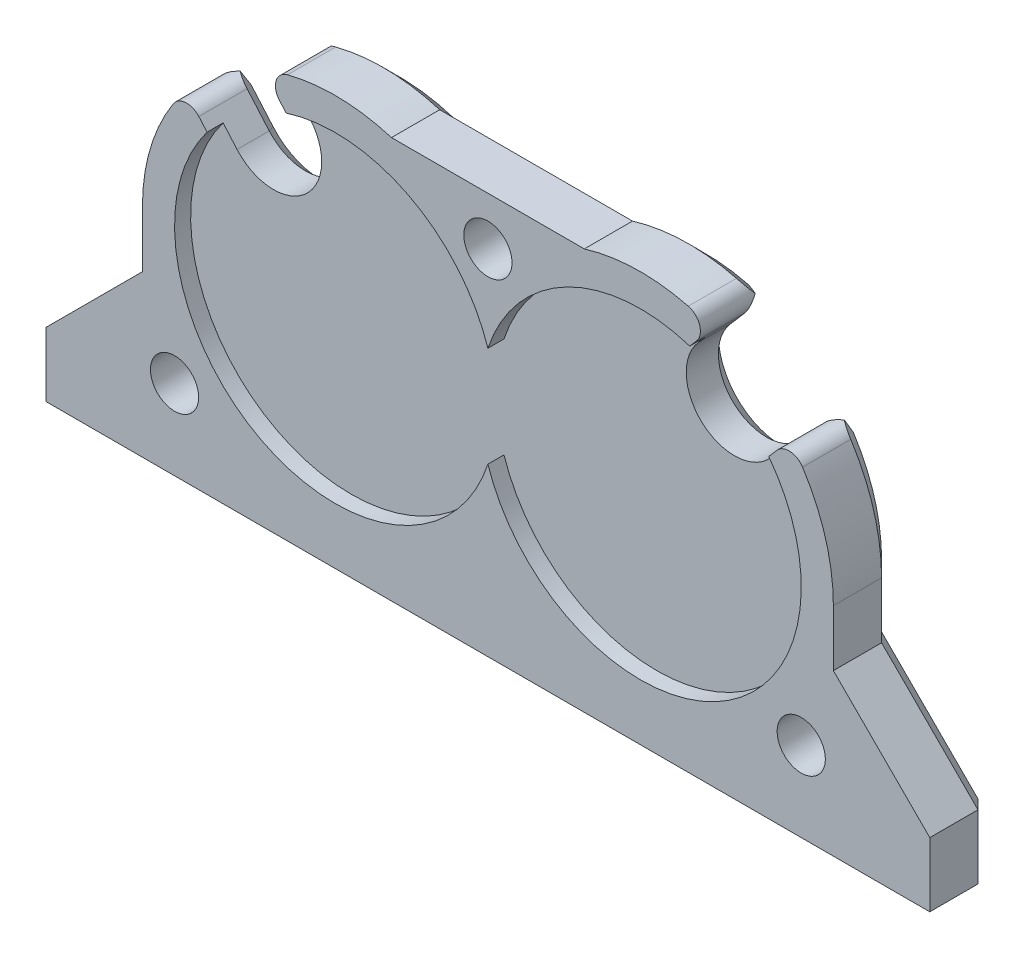
SolidWorks part; units mm, degrees
material "ABS"
ref_plane "Front Plane" through (0, 0, 0) normal (0, 0, 1) x (1, 0, 0)
ref_plane "Top Plane" through (0, 0, 0) normal (0, 1, 0) x (1, 0, 0)
ref_plane "Right Plane" through (0, 0, 0) normal (1, 0, 0) x (0, 0, -1)
sketch "Sketch1" plane through (0, 0, 0) normal (0, 0, 1) x (1, 0, 0)
  line L0 (-27.5, 0) -> (27.5, 0) construction
  line L1 (-27.5, 0) -> (-21.5, 6)
  line L2 (27.5, 0) -> (21.5, 6)
  line L3 (-9.5, 9.5) -> (9.5, 9.5) construction
  line L4 (-6, 20.9782) -> (6, 20.9782)
  line L5 (21.5, 9.5) -> (21.5, 6)
  line L6 (-21.5, 6) -> (-21.5, 9.5)
  line L7 (-27.5, 0) -> (-27.5, -4)
  line L8 (-27.5, -4) -> (27.5, -4)
  line L9 (27.5, -4) -> (27.5, 0)
  circle A0 centre (-9.5, 9.5) radius 10
  circle A1 centre (9.5, 9.5) radius 10
  arc A2 (1.1579, 3.9855) -> (1.1579, 15.0145) centre (-9.5, 9.5) ccw
  arc A3 (21.5, 9.5) -> (6, 20.9782) centre (9.5, 9.5) ccw
  arc A4 (-16.8314, 0) -> (-2.1686, 0) centre (-9.5, 9.5) ccw construction
  arc A5 (-21.5, 9.5) -> (-16.8314, 0) centre (-9.5, 9.5) ccw construction
  arc A6 (-2.1686, 0) -> (0, 2.1686) centre (-9.5, 9.5) ccw construction
  arc A7 (0, 2.1686) -> (2.1686, 0) centre (9.5, 9.5) ccw construction
  arc A8 (2.1686, 0) -> (16.8314, 0) centre (9.5, 9.5) ccw construction
  arc A9 (16.8314, 0) -> (21.5, 9.5) centre (9.5, 9.5) ccw construction
  arc A10 (0, 2.1686) -> (1.1579, 3.9855) centre (-9.5, 9.5) ccw construction
  arc A11 (-1.1579, 3.9855) -> (0, 2.1686) centre (9.5, 9.5) ccw construction
  arc A12 (6, 20.9782) -> (0, 16.8314) centre (9.5, 9.5) ccw construction
  arc A13 (-1.1579, 15.0145) -> (-1.1579, 3.9855) centre (9.5, 9.5) ccw
  arc A14 (0, 16.8314) -> (-6, 20.9782) centre (-9.5, 9.5) ccw construction
  arc A15 (-6, 20.9782) -> (-21.5, 9.5) centre (-9.5, 9.5) ccw
  arc A16 (0, 16.8314) -> (-1.1579, 15.0145) centre (9.5, 9.5) ccw construction
  arc A17 (1.1579, 15.0145) -> (0, 16.8314) centre (-9.5, 9.5) ccw construction
  point P2 (0, 0)
  point P10 (0, 9.5)
  point P22 (0, 20.9782)
  dimension "D1" = 20
  dimension "D5" = 2
  dimension "D2" = 19
  dimension "D3" = 6
  dimension "D4" = 12
  dimension "D6" = 9.5
  dimension "D7" = 4
extrude "Boss-Extrude1" add sketch "Sketch1" along normal blind 1 contours L4 A15 L6 L1 L0 L2 L5 A3 A0 A1
sketch "Sketch2" plane through (0, 0, 0) normal (0, 0, -1) x (-1, 0, 0)
  line L6 (6, 20.9782) -> (-6, 20.9782)
  line L7 (-21.5, 9.5) -> (-21.5, 6)
  line L8 (-21.5, 6) -> (-27.5, 0)
  line L9 (-27.5, 0) -> (-27.5, -4)
  line L10 (27.5, 0) -> (21.5, 6)
  line L11 (21.5, 6) -> (21.5, 9.5)
  line L12 (6, 20.9782) -> (-6, 20.9782)
  line L13 (-21.5, 9.5) -> (-21.5, 6)
  line L14 (-21.5, 6) -> (-27.5, 0)
  line L16 (27.5, 0) -> (21.5, 6)
  line L17 (21.5, 6) -> (21.5, 9.5)
  line L20 (-27.5, 0) -> (-27.5, -4)
  line L21 (-27.5, -4) -> (27.5, -4)
  line L22 (-27.5, -4) -> (27.5, -4)
  line L23 (27.5, -4) -> (27.5, 0)
  line L24 (27.5, -4) -> (27.5, 0)
  arc A2 (-6, 20.9782) -> (-21.5, 9.5) centre (-9.5, 9.5) ccw
  arc A3 (21.5, 9.5) -> (6, 20.9782) centre (9.5, 9.5) ccw
  arc A4 (-6, 20.9782) -> (-21.5, 9.5) centre (-9.5, 9.5) ccw
  arc A5 (21.5, 9.5) -> (6, 20.9782) centre (9.5, 9.5) ccw
  dimension "D1" = 0
extrude "Boss-Extrude2" add sketch "Sketch2" along normal blind 3
sketch "Sketch3" plane through (0, 0, 1) normal (0, 0, 1) x (1, 0, 0)
  line L0 (-19.5, 0.9782) -> (19.5, 0.9782) construction
  line L2 (-6, 20.9782) -> (6, 20.9782) construction
  circle A0 centre (-19.5, 0.9782) radius 1.5
  circle A1 centre (19.5, 0.9782) radius 1.5
  circle A2 centre (0, 17.9782) radius 1.5
  point P6 (0, 0.9782)
  dimension "D1" = 3
  dimension "D2" = 39
  dimension "D3" = 17
  dimension "D4" = 3
extrude "Cut-Extrude1" cut sketch "Sketch3" against normal through all
sketch "Sketch5" plane through (0, 0, -3) normal (0, 0, -1) x (-1, 0, 0)
  line L0 (-18.9376, 21.7851) -> (-14.3452, 16.5022) construction
  line L1 (-16.6735, 23.7533) -> (-12.0811, 18.4704)
  line L2 (-21.2018, 19.8169) -> (-16.6093, 14.534)
  line L3 (18.9376, 21.7851) -> (14.3452, 16.5022) construction
  line L4 (21.2018, 19.8169) -> (16.6093, 14.534)
  line L5 (16.6735, 23.7533) -> (12.0811, 18.4704)
  arc A3 (21.5, 9.5) -> (6, 20.9782) centre (9.5, 9.5) ccw construction
  arc A4 (-16.6735, 23.7533) -> (-21.2018, 19.8169) centre (-18.9376, 21.7851) ccw
  arc A5 (-16.6093, 14.534) -> (-12.0811, 18.4704) centre (-14.3452, 16.5022) ccw
  arc A6 (21.2018, 19.8169) -> (16.6735, 23.7533) centre (18.9376, 21.7851) ccw
  arc A7 (12.0811, 18.4704) -> (16.6093, 14.534) centre (14.3452, 16.5022) ccw
  arc A8 (-6, 20.9782) -> (-21.5, 9.5) centre (-9.5, 9.5) ccw construction
  point P2 (-16.6414, 19.1437)
  point P13 (16.6414, 19.1437)
  point P16 (16.6414, 19.1437)
  point P23 (-16.6414, 19.1437)
  dimension "D1" = 3
  dimension "D2" = 7
extrude "Cut-Extrude3" cut sketch "Sketch5" against normal through all
chamfer "Chamfer1" distance 1 angle 45 16 edges at (-24.5, 3, -3) (-21.5, 7.75, -3) (-10.0118, 21.4891, -3) (0, 20.9782, -3) (20.8082, 13.5157, -3) (21.5, 7.75, -3) (24.5, 3, -3) (-13.0233, 19.5543, -3) (-17.7109, 15.8011, -3) (-12.377, 14.2381, -3) (17.7109, 15.8011, -3) (13.0233, 19.5543, -3) (12.377, 14.2381, -3) (-27.5, -2, -3) (0, -4, -3) (27.5, -2, -3)
fillet "Fillet1" radius 1 7 edges at (13.9656, 20.6382, -0.5) (-18.8124, 17.0683, -0.5) (-13.9656, 20.6382, -0.5) (18.8124, 17.0683, -0.5)
sketch "Sketch4" plane through (0, 0, -3) normal (0, 0, -1) x (-1, 0, 0)
  line L0 (-19.5, 0.9782) -> (18, 0.9782) construction
  circle A1 centre (-19.5, 0.9782) radius 1.5 construction
  circle A3 centre (19.5, 0.9782) radius 1.5 construction
  text T0 "<b>Bottom</b>" font "@HP Simplified Hans" height 8
  point P5 (0, 0)
  point P6 (0, 0)
  point P7 (18, 1.9782)
extrude "Cut-Extrude2" cut sketch "Sketch4" against normal blind 0.25
